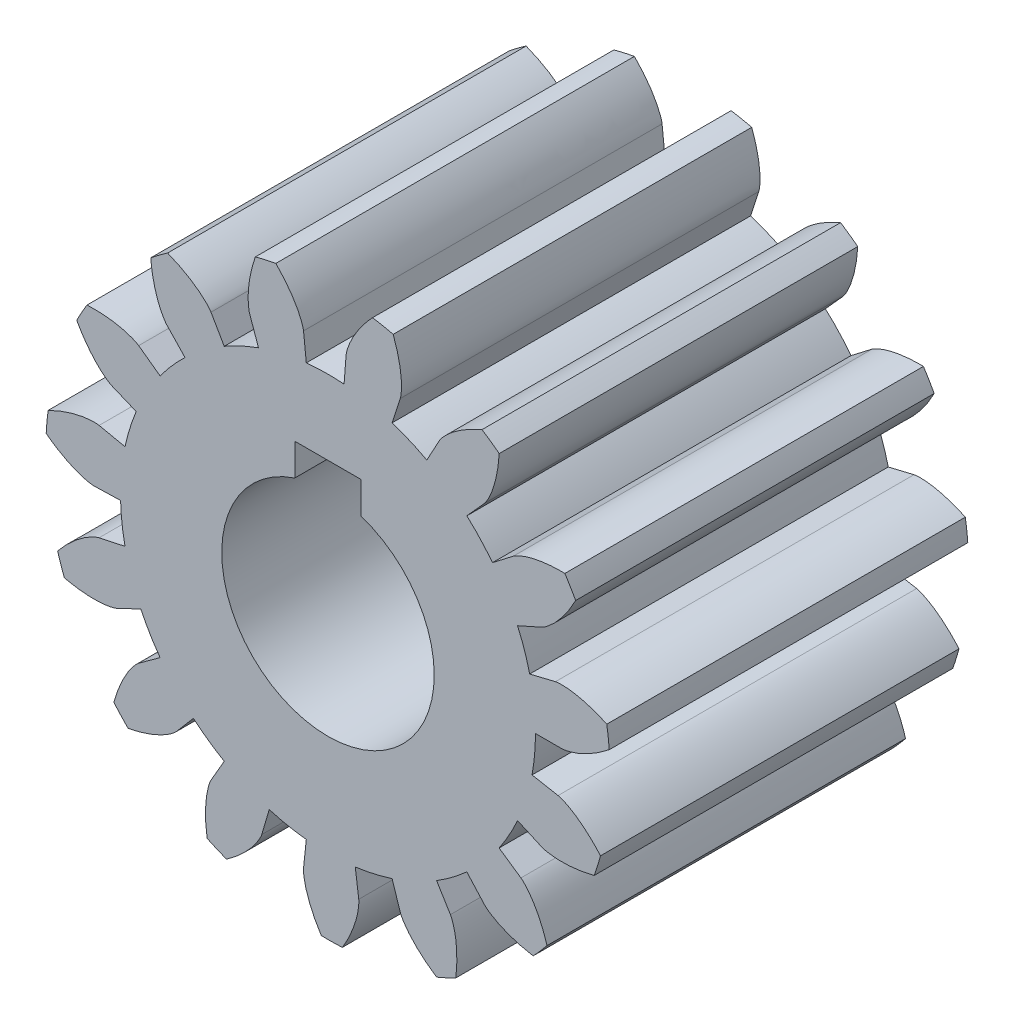
SolidWorks part; units mm, degrees
ref_plane "Front Plane" through (0, 0, 0) normal (0, 0, 1) x (1, 0, 0)
ref_plane "Top Plane" through (0, 0, 0) normal (0, 1, 0) x (1, 0, 0)
ref_plane "Right Plane" through (0, 0, 0) normal (1, 0, 0) x (0, 0, -1)
ref_plane "Plane1" through (0, 0, 0) normal (0, -1, 0) x (1, 0, 0)
sketch "Sketch3" plane through (0, 0, 0) normal (0, -1, 0) x (1, 0, 0)
  line L0 (44.8045, 0) -> (44.8045, 54)
  line L1 (44.8045, 54) -> (16, 54)
  line L2 (16, 54) -> (16, 0)
  line L3 (16, 0) -> (44.8045, 0)
  line L4 (0, 54) -> (0, 0) construction
  dimension "D1" = 16
  dimension "D2" = 44.8045
revolve "Revolve1" add sketch "Sketch3" angle 360 about L4 reverse direction yes
sketch "Sketch7" plane through (0, 0, 54) normal (0, 0, 1) x (1, 0, 0)
  circle A0 centre (0, 0) radius 42.5
  circle A1 centre (0, 0) radius 52.3763
  dimension "D1" = 85
extrude "Cut-Extrude2" cut sketch "Sketch7" against normal through all
sketch "Sketch6" plane through (0, 0, 54) normal (0, 0, 1) x (1, 0, 0)
  line L0 (35.2385, 0) -> (0, 0) construction
  line L1 (0, 0) -> (36.7733, -7.3467) construction
  line L2 (0, 0) -> (37.4958, 0.5589) construction
  line L3 (35.2385, 0) -> (56.4401, 0) construction
  line L4 (35.2385, 0) -> (31.25, 0)
  line L6 (34.6547, -6.3878) -> (30.7323, -5.6648)
  line L7 (0, 0) -> (34.6547, -6.3878) construction
  circle A0 centre (0, 0) radius 31.25 construction
  circle A1 centre (0, 0) radius 37.5 construction
  circle A2 centre (0, 0) radius 42.5 construction
  circle A3 centre (0, 0) radius 35.2385 construction
  arc A4 (31.25, 0) -> (30.7323, -5.6648) centre (0, 0) cw
  arc A6 (48.6916, 10.6127) -> (45.9611, -19.2634) centre (0, 0) cw
  spline S0 degree 4 poles (35.2385, 0) (35.2645, 0.0006) (35.3375, 0.0038) (35.4753, 0.0167) (35.6991, 0.0472) (36.1124, 0.1243) (36.7313, 0.2833) (37.4005, 0.5104) (38.0952, 0.7964) (38.6956, 1.0778) (39.1683, 1.3186) (39.7325, 1.6284) (40.3986, 2.0272) (41.1576, 2.5279) (41.9984, 3.1428) (42.8253, 3.8079) (43.6227, 4.5077) (44.3913, 5.2397) (45.0381, 5.9049) (45.5755, 6.4929) (46.0974, 7.0914) (46.523, 7.6039) (46.9323, 8.1186) (47.3374, 8.6535) (47.6437, 9.0696) (47.9643, 9.5236) (48.2398, 9.9227) (48.6343, 10.5199) (48.8641, 10.8815) (49.2267, 11.4659) (49.3796, 11.7307) (49.5219, 11.9693) (49.5614, 12.0402) (49.5915, 12.0919) (49.6078, 12.1198) knots 0 0 0 0 0 0.005377 0.015084 0.028532 0.04661 0.092111 0.146842 0.174209 0.201575 0.228941 0.256307 0.307035 0.361767 0.4165 0.471232 0.525964 0.580697 0.635429 0.662795 0.690161 0.744894 0.77226 0.799626 0.826992 0.854358 0.881725 0.909091 0.954545 0.977273 0.988636 0.994318 1 1 1 1 1 construction
  spline S1 degree 4 poles (35.2385, 0) (35.2645, 0.0006) (35.3375, 0.0038) (35.4753, 0.0167) (35.6991, 0.0472) (36.1124, 0.1243) (36.7313, 0.2833) (37.4005, 0.5104) (38.0952, 0.7964) (38.6956, 1.0778) (39.1683, 1.3186) (39.7325, 1.6284) (40.3986, 2.0272) (41.1576, 2.5279) (41.9984, 3.1428) (42.8253, 3.8079) (43.6227, 4.5077) (44.3913, 5.2397) (45.0381, 5.9049) (45.5755, 6.4929) (46.0974, 7.0914) (46.523, 7.6039) (46.9323, 8.1186) (47.3374, 8.6535) (47.6437, 9.0696) (47.9643, 9.5236) (48.2398, 9.9227) (48.4937, 10.3071) (48.6265, 10.5113) (48.6916, 10.6127) knots 0 0 0 0 0 0.005377 0.015084 0.028532 0.04661 0.092111 0.146842 0.174209 0.201575 0.228941 0.256307 0.307035 0.361767 0.4165 0.471232 0.525964 0.580697 0.635429 0.662795 0.690161 0.744894 0.77226 0.799626 0.826992 0.854358 0.881725 0.909091 0.909091 0.909091 0.909091 0.909091
  spline S2 degree 4 poles (34.6547, -6.3878) (34.6802, -6.3931) (34.7514, -6.4095) (34.8845, -6.4472) (35.0991, -6.5178) (35.4916, -6.6685) (36.0714, -6.9371) (36.6884, -7.2817) (37.3197, -7.6889) (37.8592, -8.0744) (38.2803, -8.3969) (38.7791, -8.8039) (39.3618, -9.3169) (40.0174, -9.9468) (40.7329, -10.7039) (41.4256, -11.508) (42.0829, -12.3407) (42.706, -13.1999) (43.2215, -13.9713) (43.6434, -14.647) (44.0482, -15.3302) (44.3738, -15.9113) (44.6831, -16.4917) (44.9845, -17.0912) (45.2103, -17.5559) (45.4433, -18.0605) (45.6418, -18.5029) (45.8219, -18.927) (45.9154, -19.1519) (45.9611, -19.2634) knots 0 0 0 0 0 0.005377 0.015084 0.028532 0.04661 0.092111 0.146842 0.174209 0.201575 0.228941 0.256307 0.307035 0.361767 0.4165 0.471232 0.525964 0.580697 0.635429 0.662795 0.690161 0.744894 0.77226 0.799626 0.826992 0.854358 0.881725 0.909091 0.909091 0.909091 0.909091 0.909091
  dimension "D1" = 85
  dimension "D2" = 75
  dimension "D3" = 62.5
  dimension "D4" = 70.4769
  dimension "D5" = 12.152
extrude "Cut-Extrude1" cut sketch "Sketch6" against normal through all
pattern_circular "CirPattern4" count 15 over 360 about axis through (0, 0, 54) along (0, 0, -1) of "Cut-Extrude1" reverse direction yes
ref_axis "Axis1" through (0, 0, 54) along (0, 0, -1)
sketch "Sketch8" plane through (0, 0, 54) normal (0, 0, 1) x (1, 0, 0)
  line L5 (5, 0) -> (-5, 0)
  line L6 (5, 0) -> (5, 20)
  line L7 (5, 20) -> (-5, 20)
  line L8 (-5, 0) -> (-5, 20)
  point P0 (0, 0)
  dimension "D3" = 20
  dimension "D1" = 5
  dimension "D2" = 5
extrude "Cut-Extrude3" cut sketch "Sketch8" against normal through all
equation "\"phi\"= 20"
equation "\"m\"= 5"
equation "\"Np\"= 15"
equation "\"Ng\"= 90"
equation "\"adndm_p\"= \"m\""
equation "\"ddndm_p\"= 1.25 * \"m\""
equation "\"dp\"= \"m\" * \"Np\""
equation "\"dg\"= \"m\" * \"Ng\""
equation "\"adndm_g\"= \"m\""
equation "\"ddndm_g\"= 1.25 * \"m\""
equation "\"majorDia_p\"= \"dp\" + 2 * \"m\""
equation "\"majorDia_g\"= \"dg\" + 2 * \"m\""
equation "\"rootDia_p\"= \"dp\" - 2.5 * \"m\""
equation "\"rootDia_g\"= \"dg\" - 2.5 * \"m\""
equation "\"baseDia_p\"= \"dp\" * cos ( \"phi\" )"
equation "\"baseDia_g\"= \"dg\" * cos ( \"phi\" )"
equation "\"clearance\"= \"ddndm_g\" - \"adndm_g\""
equation "\"D1@Sketch6\"=\"majorDia_p\""
equation "\"D2@Sketch6\"=\"dp\""
equation "\"D3@Sketch6\"=\"rootDia_p\""
equation "\"D4@Sketch6\"=\"baseDia_p\""
equation "\"theta_ht_p\"= 360 / 3.95 / \"Np\""
equation "\"theta_ht_g\"= 360 / 3.95 / \"Ng\""
equation "\"D1@Sketch7\"=\"majorDia_p\""
equation "\"D5@Sketch6\"=2*\"theta_ht_p\""
